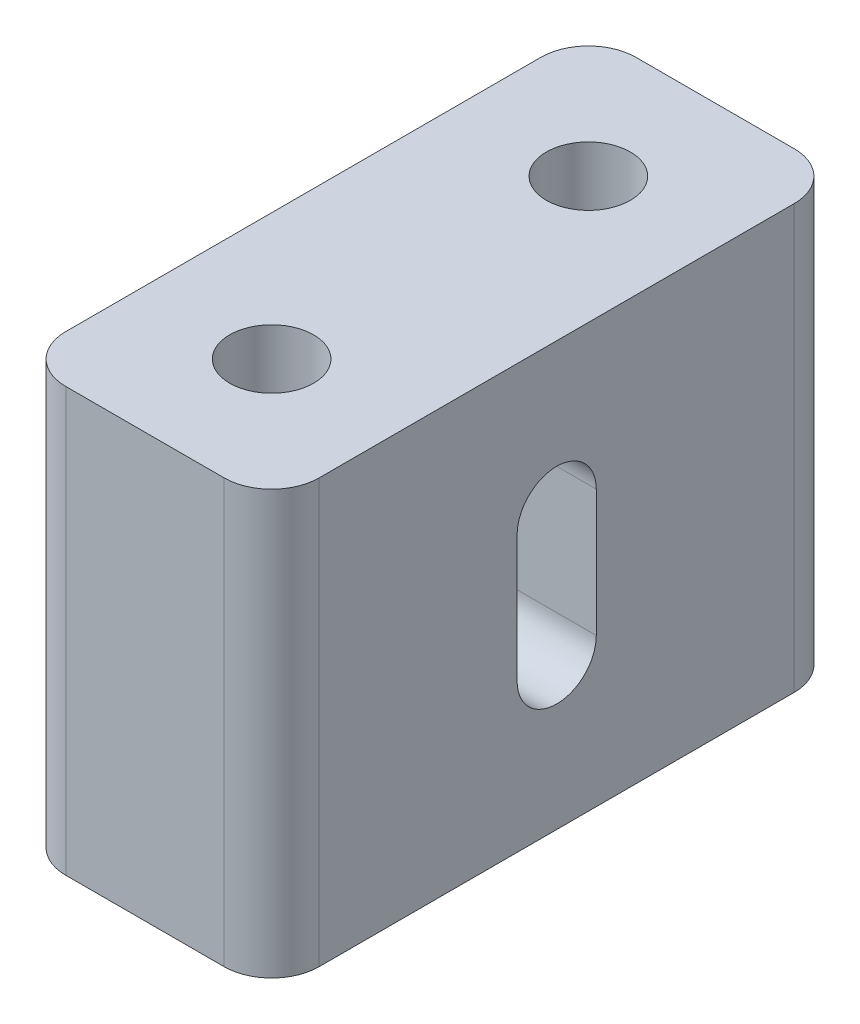
SolidWorks part; units mm, degrees
material "ABS"
ref_plane "Front Plane" through (0, 0, 0) normal (0, 0, 1) x (1, 0, 0)
ref_plane "Top Plane" through (0, 0, 0) normal (0, 1, 0) x (1, 0, 0)
ref_plane "Right Plane" through (0, 0, 0) normal (1, 0, 0) x (0, 0, -1)
sketch "Sketch1" plane through (0, 0, 0) normal (0, 1, 0) x (1, 0, 0)
  line L0 (-8, 5) -> (8, 5) construction
  line L1 (-8, -18) -> (8, -18)
  line L2 (-8, -18) -> (-8, 18)
  line L3 (-8, 18) -> (8, 18)
  line L4 (8, -18) -> (8, 18)
  line L5 (-8, -18) -> (8, 18) construction
  line L6 (-8, 18) -> (8, -18) construction
  line L7 (8, -5) -> (-8, -5) construction
  line L8 (-8, -5) -> (8, 5) construction
  circle A0 centre (0, 10) radius 5 construction
  circle A1 centre (0, -10) radius 5 construction
  circle A2 centre (0, 10) radius 8 construction
  point P0 (0, 0)
  point P12 (0, 0)
  dimension "D2" = 10
  dimension "D1" = 10
  dimension "D3" = 3
extrude "Boss-Extrude1" add sketch "Sketch1" along normal mid plane 26.7324 contours L3 L4 L1 L2
hole_wizard "M5 Clearance Hole1" positions "Sketch2" profile "Sketch3" hole size "M5" standard "ANSI Metric" end condition through all
sketch "Sketch2" plane through (0, 13.3662, 0) normal (0, 1, 0) x (1, 0, 0)
  point P0 (0, 10)
  point P3 (0, -10)
sketch "Sketch3" plane through (0, 13.3662, -10) normal (1, 0, 0) x (0, 0, 1)
  line L0 (0, 0) -> (0, 26.7324)
  line L1 (0, 26.7324) -> (2.65, 26.7324)
  line L2 (2.65, 26.7324) -> (2.65, 0)
  line L5 (2.65, 0) -> (0, 0)
  line L11 (0, -6.35) -> (0, 107.95) construction
  dimension "Thru Hole Dia." = 5.3
  dimension "Thru Hole Depth" = 26.7324
fillet "Fillet1" radius 3 4 edges at (-8, 0, -18) (8, 0, -18) (-8, 0, 18) (8, 0, 18)
sketch "Sketch6" plane through (0, 0, 0) normal (1, 0, 0) x (0, 0, -1)
  line L0 (0, -4) -> (0, 4) construction
  line L1 (-2.5, -4) -> (-2.5, 4)
  line L2 (2.5, -4) -> (2.5, 4)
  arc A0 (-2.5, -4) -> (2.5, -4) centre (0, -4) ccw
  arc A1 (2.5, 4) -> (-2.5, 4) centre (0, 4) ccw
  point P2 (0, 0)
  dimension "D1" = 2.5
  dimension "D2" = 8
extrude "Cut-Extrude1" cut sketch "Sketch6" against normal through all both and the other way through all
equation "\"ExtrusionStandard\"= 20mm'Size of extrusion used for framing"
equation "\"BaseExtrusionFrameWidth\"= 60mm'Width of the central aluminum extrusion"
equation "\"BaseExtrusionFrameHeight\"= 20mm'Height of the central aluminum extrusion"
equation "\"PlateThickness\"= 15mm'Thickness of the the front and back framing plates"
equation "\"RailHeight\"= 13mm'Total height of the carriage and rail component"
equation "\"WallThickness\"= 3mm'Standard wall thickness"
equation "\"ShaftDiameter\"= 20mm'Outside Diameter of the main yoke shaft"
equation "\"ShaftClearance\"= 1mm'Clearance/gap between the main yoke and non-bearing elements"
equation "\"PlainBearingBoltCircleDiameter\"= ( \"WallThickness\" + \"M3_ClearanceDiameter\" / 2 ) * 2 + \"PlainBearingOD\"'Bolt circle diameter for the plain bearing retainer/mount"
equation "\"PlainBearingBoltcount\"= 5'Number of bolts used in the plain bearing/mount"
equation "\"X_ThrustBearingOD\"= 35mm'OD of the thrust bearing used on the main shaft"
equation "\"X_ThrustBearingID\"= 20mm'ID of the thrust bearing used on the main shaft"
equation "\"X_ThrustBearingThickness\"= 10mm'Thickness of the thrust bearing used on the main shaft"
equation "\"X_RearCollarOD\"= 32mm'OD of the shaft collar of the main shaft"
equation "\"X_RearCollarID\"= 20mm'ID of the shaft collar of the main shaft"
equation "\"X_RearCollarThickness\"= 8mm'Thickness of the collar along the main shaft"
equation "\"LeadScrewDiameter\"= 6.35mm'OD of the leadsrew used on the Y axis"
equation "\"LeadScrewHeight\"= 10mm'Height of the center of the Lead screw from bottom of gantry extrusion"
equation "\"LeadScrewNut_FlangeOD\"= 25mm'OD of the lead screw nut flange"
equation "\"LeadScrewNut_BoltCircleDiameter\"= 19mm'Bolt circle diameter needed to mount the leadscrew nut"
equation "\"LeadScrewNut_BoltCount\"= 6'Number of bolts required to mount the leadscrew nut to gantry."
equation "\"Pillow_BaseClearance\"= 6mm + \"WallThickness\"'Pillow block base needed to internally mount screws"
equation "\"X_PillowHeight\"= \"Pillow_BaseClearance\" + \"calc_X_PillowRadius\"'Height of the main shaft pillow block base, as measured from the top of the gantry surface"
equation "\"X_BeltPitch\"= 2mm'Pitch of the timing belt used on the X axis/main shaft."
equation "\"X_Drive_Teeth\"= 20'Number of teeth used on the X/Main stepper motor pulley"
equation "\"X_Shaft_Teeth\"= 60'Number of teeth on the X/Main shaft pulley"
equation "\"X_Drive_PD\"= ( \"X_Drive_Teeth\" * \"X_BeltPitch\" ) / PI'Pitch Diameter of the X/main motor pulley"
equation "\"X_Shaft_PD\"= ( \"X_Shaft_Teeth\" * \"X_BeltPitch\" ) / PI'Pitch Diameter of the X/main shaft pulley"
equation "\"X_CenterDistance\"= 55mm'Distance between the main shaft and motor pulley centers"
equation "\"GantryLength\"= 150mm'Length of the gantry extrusion/plate"
equation "\"X_MotorPlateThickness\"= 15mm'Thickness of the plate used to hold the X/main motor"
equation "\"X_MotorPlateLength\"= \"X_MotorPlateThickness\" + \"ExtrusionStandard\" * 2'FIXME"
equation "\"X_BeltWidth\" = 9mm'Width of the timing belt used on the X/Main shaft rotary drive"
equation "\"X_PillowLength\"= ( \"WallThickness\" * 4 ) + \"X_RearCollarThickness\" + ( \"X_ThrustBearingThickness\" * 2 ) + \"X_ShaftRotaryBearingThickness\"'Total length of the pillow block used to hold the main shaft"
equation "\"X_ShaftRotaryBearingThickness\"= 9mm'Thickness of the radial bearing used on the main shaft"
equation "\"X_ShaftRotaryBearingOD\"= 37mm'OD of the radial bearing used on the main shaft"
equation "\"ShaftLength\"= 400mm'Length of the main shaft."
equation "\"PlainBearingOD\"= 31.8mm'OD of the Plain Bearing housing"
equation "\"Y_Drive_Length\"= \"ShaftLength\"'duplicate"
equation "\"Y_Drive_Diameter\"= \"LeadScrewDiameter\"'duplicate"
equation "\"Y_Drive_ThrustBearingOD\"= .5625in'OD of the thrust bearings used to support the leadscrew/Y drive"
equation "\"Y_Drive_ThrustBearingThickness\"= .193in'Thickness of the thrust bearings used to support the leadscrew/Y drive"
equation "\"Y_Drive_ShaftCollarOD\"= .6875in'OD of the collar used to constrain the leadscrew/Y drive"
equation "\"Y_Drive_ShaftCollarThickness\"= .3125in'Thickness of the collar used to constrain the leadscrew/Y drive"
equation "\"Y_Drive_ShaftCollarClearance\"= .375in / 2'Amount of radial clearance needed around the leadscrew/Y shaft collar"
equation "\"calc_Y_Drive_BearingLargestDiameter\"= IIF ( \"Y_Drive_ThrustBearingOD\" > \"Y_Drive_ShaftCollarOD\" , \"Y_Drive_ThrustBearingOD\" , \"Y_Drive_ShaftCollarOD\" )'FIXME - calculated diameter needed for Y drive pillow - needs to account for collar clearance."
equation "\"Y_Drive_BearingBoltCircleDiameter\"= \"calc_Y_Drive_BearingLargestDiameter\" + ( \"Y_Drive_ShaftCollarClearance\" * 2 ) + ( \"WallThickness\" * 2 ) + 2 * 10mm'FIXME - unused?"
equation "\"M3_ClearanceDiameter\"= 8mm'Keepout diameter for M3 holes"
equation "\"M5_ClearanceDiameter\"= 10mm'Keepout Diameter for M5 holes"
equation "\"Y_Drive_CenterDistance\"= 65mm'Center Distance between Y motor drive and leadscrew pulley"
equation "\"Y_Drive_Teeth\"= 20'Number of teeth on the Y/linear stepper pulley"
equation "\"Y_Drive_ShaftTeeth\"= 60'Number of teeth on the Y/linear leadscrew pulley"
equation "\"Y_Drive_BeltWidth\"= 9mm'Width of the belt used on the Y/linear drive"
equation "\"Y_Drive_BeltPitch\"= 2mm'Pitch of the timing belt used on the Y/linear drive"
equation "\"Y_Drive_PD\"= ( \"Y_Drive_Teeth\" * \"Y_Drive_BeltPitch\" ) / PI'Pitch Diameter of the stepper pulley for the Y/linear drive"
equation "\"Y_Drive_ShaftPD\"= ( \"Y_Drive_ShaftTeeth\" * \"Y_Drive_BeltPitch\" ) / PI'Pitch diameter of the pulley on the Y/linear leadscrew"
equation "\"PlainBearingLength\"= 44.8mm'Length of the plain bearing housing"
equation "\"Y_Drive_ShaftBearingThickness\"= .196in'Thickness of the radial bearing used to support the Y leadscrew"
equation "\"Y_Drive_ShaftBearingOD\"= .625in'OD of the radial bearing used to support the Y leadscrew"
equation "\"EncoderMount_BoltWidth\"= 80mm"
equation "\"EncoderMount_BoltRowCount\" = 1"
equation "\"EncoderMount_BoltRowDistance\"= 20mm"
equation "\"EncoderMount_Offset\"= 10mm"
equation "\"Y_Drive_StepperShaftLength\"= 21mm"
equation "\"X_StepperShaftLength\" = 21mm"
equation "\"Y_DriveStepperShaftDiameter\"= 6.35mm"
equation "\"X_StepperShaftDiameter\"= 6.35mm"
equation "\"calc_X_PillowRadius\"= IIF ( ( \"X_ThrustBearingOD\" / 2 ) > ( \"X_RearCollarOD\" / 2 * 1.5 ) , \"X_ThrustBearingOD\" / 2 , ( \"X_RearCollarOD\" / 2 ) * 1.5 ) + ( \"WallThickness\" )'Minimum Radius needed for X/main shaft pillow block elements."
equation "\"calc_Y_PillowRadius\"= IIF ( \"Y_Drive_ThrustBearingOD\" / 2 > ( \"Y_Drive_ShaftCollarOD\" / 2 * 1.5 ) , \"Y_Drive_ThrustBearingOD\" / 2 , ( \"Y_Drive_ShaftCollarOD\" / 2 ) * 1.5 )'Minimum radius needed for the Y/linear shaft pillow block elements"
equation "\"Y_PillowHeight\"= \"Pillow_BaseClearance\" + \"calc_Y_PillowRadius\"'Height of the Y/linear pillow block base"
equation "\"Assembly_MainShaftStickout\"= 50mm'Amount of stickout at maximum pitch down (yoke forward)"
equation "\"GantryHeight\"= \"ExtrusionStandard\"'Height of the Gantry, including carriage mounting brackets"
equation "\"Y_StepperFrameSize\"= 57mm"
equation "\"Y_StepperHoleMountingDistance\"= 47mm"
equation "\"SidePanelHeight\" = \"Y_StepperFrameSize\" / 2 + \"X_CenterDistance\" + \"X_PillowHeight\" + \"GantryHeight\" + \"RailHeight\" + \"ExtrusionStandard\" - ( \"ExtrusionStandard\" * 3 ) + \"TopClearance\""
equation "\"TopClearance\"= 5mm"
equation "\"ExtrusionLength\"= 400mm"
equation "\"TopPanelWidth\" = 150mm"
equation "\"BodyPanelThickness\"= .25in'Thickness of side and top body panels."
equation "\"D1@Sketch1\"=\"M5_ClearanceDiameter\""
equation "\"D2@Sketch1\"=\"M5_ClearanceDiameter\""
equation "\"D3@Sketch1\"=\"WallThickness\""
equation "\"D1@Boss-Extrude1\"=\"X_Drive_PD\"+\"WallThickness\"*2+\"M3_ClearanceDiameter\""
equation "\"D1@Fillet1\"=\"WallThickness\""
equation "\"D1@Sketch6\"=5mm/2"
equation "\"D2@Sketch6\"=\"M3_ClearanceDiameter\""
